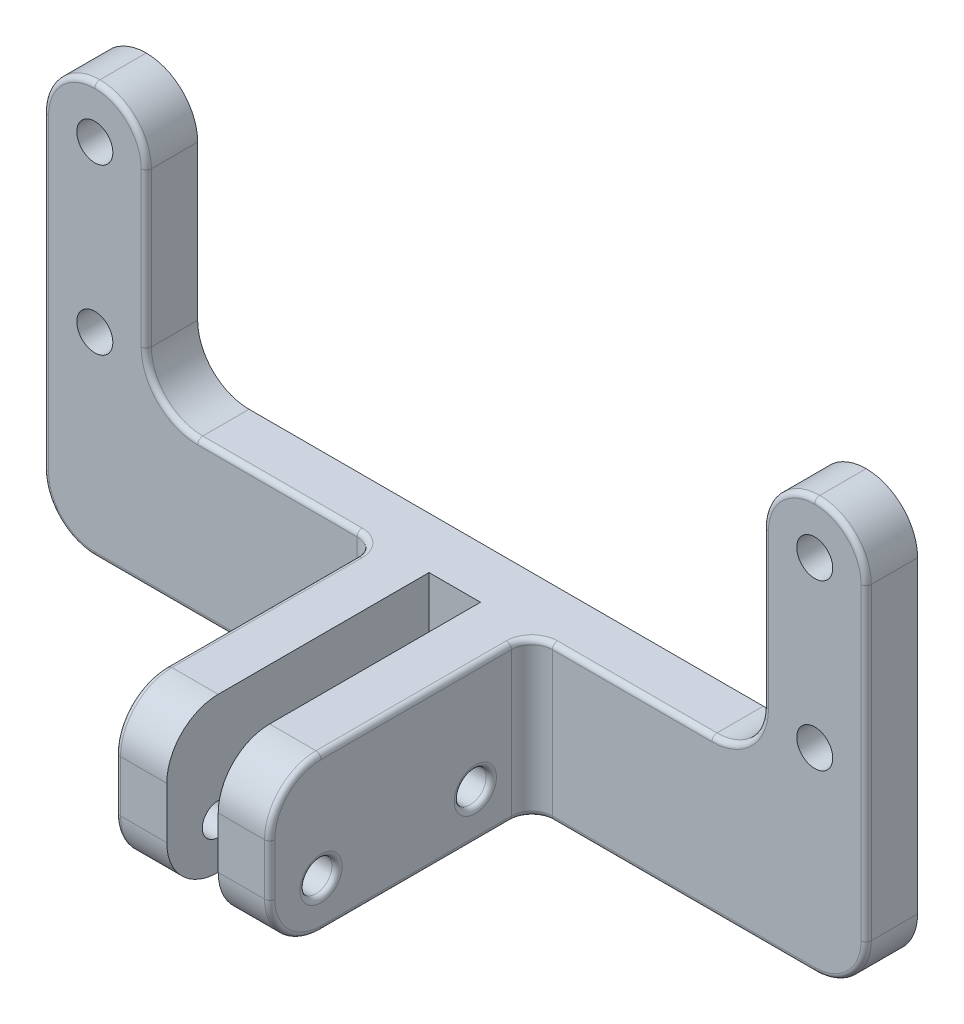
SolidWorks part; units mm, degrees
ref_plane "正面" through (0, 0, 0) normal (0, 0, 1) x (1, 0, 0)
ref_plane "平面" through (0, 0, 0) normal (0, 1, 0) x (1, 0, 0)
ref_plane "右側面" through (0, 0, 0) normal (1, 0, 0) x (0, 0, -1)
sketch "ｽｹｯﾁ1" plane through (0, 0, 0) normal (0, 0, 1) x (1, 0, 0)
  line L1 (40, 20) -> (-40, 20)
  line L2 (40, 20) -> (40, -20)
  line L3 (40, -20) -> (-40, -20)
  line L4 (-40, 20) -> (-40, -20)
  line L5 (40, 20) -> (-40, -20) construction
  line L6 (40, -20) -> (-40, 20) construction
  point P0 (0, 0)
  dimension "D1" = 80
  dimension "D2" = 40
extrude "ﾎﾞｽ - 押し出し1" add sketch "ｽｹｯﾁ1" along normal blind 5
sketch "ｽｹｯﾁ2" plane through (0, 0, 0) normal (0, 0, 1) x (1, 0, 0)
  line L0 (40, -20) -> (40, 20) construction
  line L1 (40, 20) -> (-40, 20) construction
  line L2 (0, 20) -> (0, -20) construction
  line L3 (-40, -20) -> (40, -20) construction
  circle A0 centre (35, 15) radius 1.75
  circle A1 centre (35, -1) radius 1.75
  circle A2 centre (-35, 15) radius 1.75
  circle A3 centre (-35, -1) radius 1.75
  dimension "D1" = 3.5
  dimension "D2" = 3.5
  dimension "D3" = 5
  dimension "D4" = 5
  dimension "D5" = 0
  dimension "D6" = 16
extrude "ｶｯﾄ - 押し出し1" cut sketch "ｽｹｯﾁ2" along normal through all
sketch "ｽｹｯﾁ3" plane through (0, 0, 5) normal (0, 0, 1) x (1, 0, 0)
  line L0 (0, 20) -> (0, -20) construction
  line L1 (40, 20) -> (-40, 20) construction
  line L2 (-40, -20) -> (40, -20) construction
  line L3 (7.5, -20) -> (7.5, -5)
  line L4 (-2.5, -20) -> (-7.5, -20)
  line L5 (-2.5, -20) -> (-2.5, -5)
  line L6 (-2.5, -5) -> (-7.5, -5)
  line L7 (-7.5, -20) -> (-7.5, -5)
  line L8 (2.5, -5) -> (7.5, -5)
  line L9 (2.5, -20) -> (2.5, -5)
  line L10 (2.5, -20) -> (7.5, -20)
  dimension "D1" = 2.5
  dimension "D2" = 15
  dimension "D3" = 5
extrude "ﾎﾞｽ - 押し出し2" add sketch "ｽｹｯﾁ3" along normal blind 25.5
sketch "ｽｹｯﾁ4" plane through (-7.5, 0, 0) normal (-1, 0, 0) x (0, 0, 1)
  line L0 (30.5, -20) -> (5, -20) construction
  line L1 (5, -5) -> (5, -20) construction
  circle A0 centre (10.5, -15.5) radius 1.55
  circle A1 centre (25.5, -15.5) radius 1.55
  dimension "D1" = 3.1
  dimension "D2" = 5.5
  dimension "D3" = 3.1
  dimension "D4" = 15
  dimension "D5" = 4.5
extrude "ｶｯﾄ - 押し出し2" cut sketch "ｽｹｯﾁ4" against normal through all
sketch "ｽｹｯﾁ5" plane through (0, 0, 0) normal (0, 0, 1) x (1, 0, 0)
  line L0 (40, 20) -> (-40, 20) construction
  line L1 (30, 20) -> (-30, 20)
  line L2 (30, 20) -> (30, -5)
  line L3 (30, -5) -> (-30, -5)
  line L4 (-30, 20) -> (-30, -5)
  line L5 (40, -20) -> (40, 20) construction
  line L6 (-40, 20) -> (-40, -20) construction
  dimension "D1" = 25
  dimension "D2" = 10
  dimension "D3" = 10
extrude "ｶｯﾄ - 押し出し3" cut sketch "ｽｹｯﾁ5" along normal blind 5
fillet "ﾌｨﾚｯﾄ1" radius 5 4 edges at (5, -5, 30.5) (-5, -5, 30.5) (5, -20, 30.5) (-5, -20, 30.5)
fillet "ﾌｨﾚｯﾄ2" radius 5 8 edges at (-30, -5, 2.5) (30, -5, 2.5) (30, 20, 2.5) (40, 20, 2.5) (40, -20, 2.5) (-40, -20, 2.5) (-30, 20, 2.5) (-40, 20, 2.5)
fillet "ﾌｨﾚｯﾄ3" radius 2 2 edges at (7.5, -12.5, 5)
fillet "ﾌｨﾚｯﾄ4" radius 0.5 34 edges at (8.0858, -5, 5.5858) (17.25, -5, 5) (28.5355, -3.5355, 5) (30, 7.5, 5) (31.4645, 18.5355, 5) (38.5355, 18.5355, 5) (40, 0, 5) (38.5355, -18.5355, 5) (8.0858, -20, 5.5858) (-8.0858, -20, 5.5858) (-38.5355, -18.5355, 5) (-40, 0, 5) (-38.5355, 18.5355, 5) (-31.4645, 18.5355, 5) (-30, 7.5, 5) (-28.5355, -3.5355, 5) (-17.25, -5, 5) (-8.0858, -5, 5.5858) (7.5, -18.5355, 29.0355) (7.5, -12.5, 30.5) (7.5, -6.4645, 29.0355) (7.5, -5, 16.25) (7.5, -20, 16.25) (7.5, -17.05, 10.5) (7.5, -17.05, 25.5) (-7.5, -6.4645, 29.0355) (-7.5, -12.5, 30.5) (-7.5, -18.5355, 29.0355) (-7.5, -5, 16.25) (-7.5, -15.5, 12.05) (-7.5, -15.5, 27.05)
